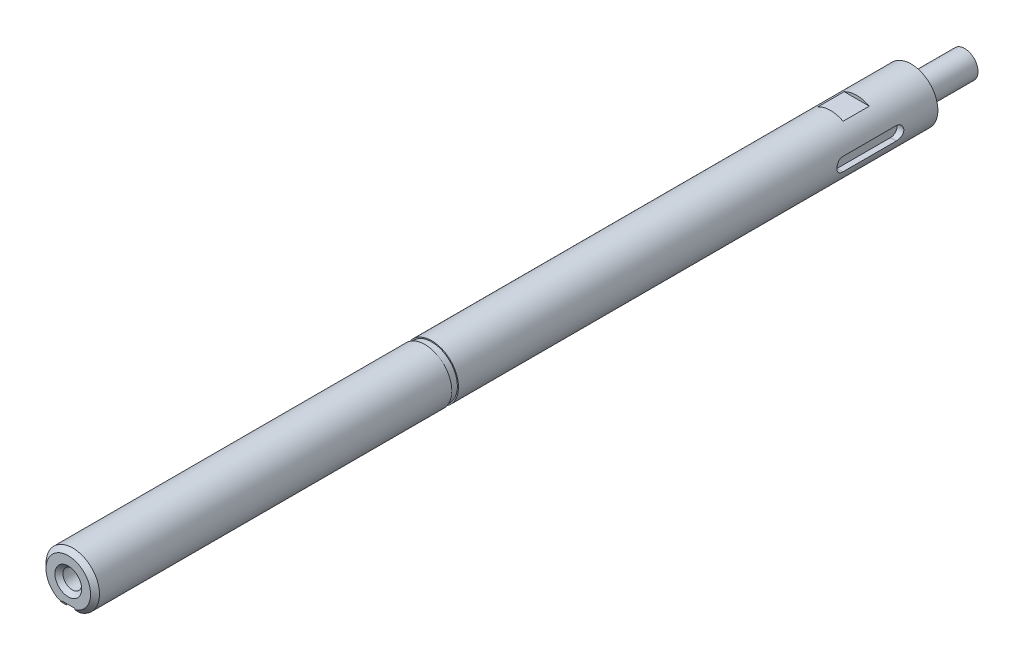
SolidWorks part; units mm, degrees
material "1.2210 (115CrV3)"
ref_plane "Front Plane" through (0, 0, 0) normal (0, 0, 1) x (1, 0, 0)
ref_plane "Top Plane" through (0, 0, 0) normal (0, 1, 0) x (1, 0, 0)
ref_plane "Right Plane" through (0, 0, 0) normal (1, 0, 0) x (0, 0, -1)
sketch "Sketch1" plane through (0, 0, 0) normal (1, 0, 0) x (0, 0, -1)
  line L0 (0, 0) -> (0, 6)
  line L8 (107.1, 6) -> (107.1, 0)
  line L9 (107.1, 0) -> (0, 0)
  line L10 (-38.6361, 0) -> (0, 0) construction
  line L18 (107.1, 6) -> (0, 6)
  dimension "D1" = 107.1
  dimension "D16" = 12
revolve "Revolve1" add sketch "Sketch1" angle 360 about L10
ref_plane "Plane3" through (0, 0, -107.1) normal (0, 0, -1) x (-1, 0, 0)
sketch "Sketch18" plane through (0, 0, 0) normal (0, 0, 1) x (1, 0, 0)
  circle A0 centre (0, 0) radius 6
  dimension "D1" = 12
extrude "Boss-Extrude1" add sketch "Sketch18" along normal blind 72.5
sketch "Sketch19" plane through (0, 0, 0) normal (0, 1, 0) x (1, 0, 0)
  line L0 (0, -63.9) -> (0, -51.9) construction
  line L1 (-1.5, -63.9) -> (-1.5, -51.9)
  line L2 (1.5, -63.9) -> (1.5, -51.9)
  line L3 (-6, -72.5) -> (6, -72.5) construction
  arc A0 (-1.5, -63.9) -> (1.5, -63.9) centre (0, -63.9) ccw
  arc A1 (1.5, -51.9) -> (-1.5, -51.9) centre (0, -51.9) ccw
  point P2 (0, -57.9)
  dimension "D1" = 3
  dimension "D2" = 12
  dimension "D3" = 8.6
extrude "Cut-Extrude4" cut sketch "Sketch19" against normal up to surface (1.3095 mm away) from offset 4.5 up to face at (6, 0, -107.1) offset against normal yes
hole_wizard "M5 Tapped Hole3" positions "Sketch21" profile "Sketch20" tap size "M5" standard "ISO"
sketch "Sketch21" plane through (0, 0, 72.5) normal (0, 0, 1) x (1, 0, 0)
  point P0 (0, 0)
sketch "Sketch20" plane through (0, 0, 72.5) normal (1, 0, 0) x (0, -1, 0)
  line L0 (0, 0) -> (0, 15.2618)
  line L1 (0, 15.2618) -> (2.1, 14)
  line L2 (2.1, 14) -> (2.1, 0.9)
  line L3 (2.1, 0.9) -> (3, 0)
  line L5 (3, 0) -> (0, 0)
  line L6 (-2.1, 0.9) -> (-3, 0) construction
  line L10 (0, 15.2618) -> (-2.1, 14) construction
  line L11 (0, -6.35) -> (0, 107.95) construction
  dimension "Tap Drill Dia." = 4.2
  dimension "Tap Drill Depth" = 14
  dimension "Near C'Sink Dia." = 6
  dimension "Near C'Sink Angle" = 90
  dimension "Drill Angle" = 118
cosmetic thread "Hole Thread18" parameters "D1"=10, "D2"=5
sketch "Sketch22" plane through (0, 0, -107.1) normal (0, 0, -1) x (-1, 0, 0)
  circle A1 centre (0, 0) radius 6
  circle A2 centre (0, 0) radius 6
  dimension "D1" = 0
extrude "Boss-Extrude2" add sketch "Sketch22" along normal offset from surface (21.4 mm away) 21.4 up to plane "Plane3"
cosmetic thread "Cosmetic Thread1" [suppressed]
chamfer "Chamfer2" distance 1 angle 45 1 edges at (6, 0, 72.5)
sketch "Sketch25" plane through (0, 0, 72.5) normal (0, 0, 1) x (1, 0, 0)
  line L0 (-1.5, -7.5) -> (-1.5, -4.5)
  line L1 (-1.5, -7.5) -> (1.5, -7.5)
  line L2 (-1.5, -4.5) -> (1.5, -4.5)
  line L3 (1.5, -7.5) -> (1.5, -4.5)
  line L4 (-1.5, -7.5) -> (1.5, -4.5) construction
  line L5 (-1.5, -4.5) -> (1.5, -7.5) construction
  line L6 (0, 0) -> (0, -6) construction
  circle A0 centre (0, 0) radius 6 construction
  point P1 (0, -6)
  dimension "D1" = 3
extrude "Cut-Extrude5" cut sketch "Sketch25" against normal blind 30
fillet "Fillet2" radius 1.5 2 edges at (1.5, -5.1547, 42.5) (-1.5, -5.1547, 42.5)
sketch "Sketch30" plane through (0, 0, -128.5) normal (0, 0, -1) x (-1, 0, 0)
  circle A0 centre (0, 0) radius 3
  dimension "D1" = 6
extrude "Cut-Extrude10" cut sketch "Sketch30" against normal blind 12 flip side to cut
sketch "Sketch31" plane through (0, 0, 0) normal (1, 0, 0) x (0, 0, -1)
  line L0 (104.3, -28.1196) -> (104.3, -5.3)
  line L1 (104.3, -28.1196) -> (98.43, -28.1196)
  line L2 (104.3, -5.3) -> (98.43, -5.3)
  line L3 (98.43, -28.1196) -> (98.43, -5.3)
  line L4 (104.3, -28.1196) -> (98.43, -5.3) construction
  line L5 (104.3, -5.3) -> (98.43, -28.1196) construction
  line L6 (104.3, 28.1555) -> (104.3, 5.3)
  line L7 (104.3, 28.1555) -> (98.43, 28.1555)
  line L8 (104.3, 5.3) -> (98.43, 5.3)
  line L9 (98.43, 28.1555) -> (98.43, 5.3)
  line L10 (104.3, 28.1555) -> (98.43, 5.3) construction
  line L11 (104.3, 5.3) -> (98.43, 28.1555) construction
  line L12 (98.43, -5.3) -> (98.43, 5.3) construction
  line L13 (98.43, 5.3) -> (98.5751, 6.4403) construction
  line L14 (0, 0) -> (98.43, 0) construction
  line L15 (116.5, -6) -> (116.5, 6) construction
  point P1 (101.365, -16.7098)
  point P2 (101.365, 16.7278)
  dimension "D1" = 5.87
  dimension "D2" = 12.2
  dimension "D3" = 10.6
extrude "Cut-Extrude11" cut sketch "Sketch31" against normal through all both and the other way through all
sketch "Sketch32" plane through (0, 0, 0) normal (1, 0, 0) x (0, 0, -1)
  line L0 (107.365, 0) -> (95.365, 0) construction
  line L1 (107.365, -1.5) -> (95.365, -1.5)
  line L2 (107.365, 1.5) -> (95.365, 1.5)
  line L3 (101.365, 5.3) -> (101.365, -5.3) construction
  line L4 (104.3, 5.3) -> (98.43, 5.3) construction
  arc A0 (107.365, -1.5) -> (107.365, 1.5) centre (107.365, 0) ccw
  arc A1 (95.365, 1.5) -> (95.365, -1.5) centre (95.365, 0) ccw
  point P2 (101.365, 0)
  dimension "D1" = 3
  dimension "D2" = 12
extrude "Cut-Extrude12" cut sketch "Sketch32" along normal through all from offset 4.5
ref_plane "Plane4" through (0, 0, 41.3) normal (0, 0, -1) x (-1, 0, 0)
sketch "Sketch33" plane through (0, 0, 41.3) normal (0, 0, -1) x (-1, 0, 0)
  circle A0 centre (0, 0) radius 5.75
  dimension "D1" = 11.5
extrude "Cut-Extrude13" cut sketch "Sketch33" against normal blind 1.5 from offset 50.3 flip side to cut
move or copy body "Body-Move/Copy1" [suppressed] bodies to move or copy 120
sketch "Sketch29" [suppressed] plane through (0, 0, 107.1) normal (0, 0, 1) x (1, 0, 0)
  circle A0 centre (0, 0) radius 13.0375
ref_plane "Plane2" [suppressed] through (0, 0, 107.1) normal (0, 0, 1) x (1, 0, 0)
sketch "Sketch28" [suppressed] plane through (0, 0, -72.5) normal (0, 0, -1) x (-1, 0, 0)
  circle A0 centre (0, 0) radius 10.9947
sketch "Sketch27" [suppressed] plane through (0, 0, 128.5) normal (0, 0, 1) x (1, 0, 0)
  circle A0 centre (0, 0) radius 3
  dimension "D1" = 6
extrude "Cut-Extrude7" [suppressed] cut sketch "Sketch27" against normal blind 12 flip side to cut
extrude "Cut-Extrude8" [suppressed] cut sketch "Sketch28" against normal blind 50
equation "\"mm\"=40"
